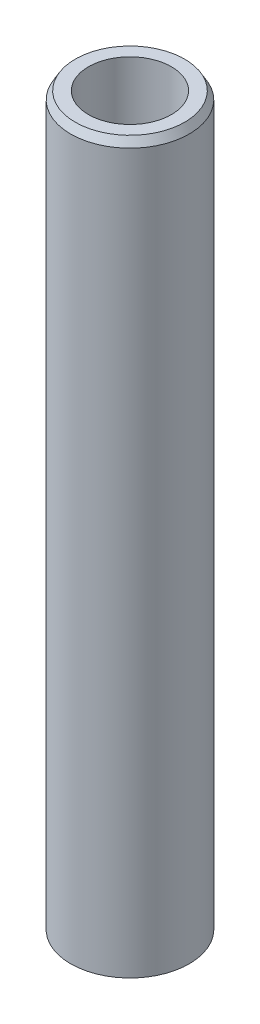
SolidWorks part; units mm, degrees
ref_plane "Front Plane" through (0, 0, 0) normal (0, 0, 1) x (1, 0, 0)
ref_plane "Top Plane" through (0, 0, 0) normal (0, 1, 0) x (1, 0, 0)
ref_plane "Right Plane" through (0, 0, 0) normal (1, 0, 0) x (0, 0, -1)
sketch "Sketch1" plane through (0, 0, 0) normal (0, 1, 0) x (1, 0, 0)
  circle A0 centre (0, 0) radius 37.5
  dimension "SHAFT_OD" = 75
extrude "Boss-Extrude1" add sketch "Sketch1" along normal blind 462.5363
sketch "Sketch2" plane through (0, 0, 0) normal (0, 1, 0) x (1, 0, 0)
  circle A0 centre (0, 0) radius 26.2435
  dimension "BORE_D" = 52.487
extrude "Cut-Extrude1" cut sketch "Sketch2" along normal through all
chamfer "Chamfer1" distance 5.02 angle 30 2 edges at (0, 462.5363, 37.5) (0, 0, 37.5) first distance on face at (0, 462.5363, 37.5) first distance on face at (0, 0, 26.2435)
